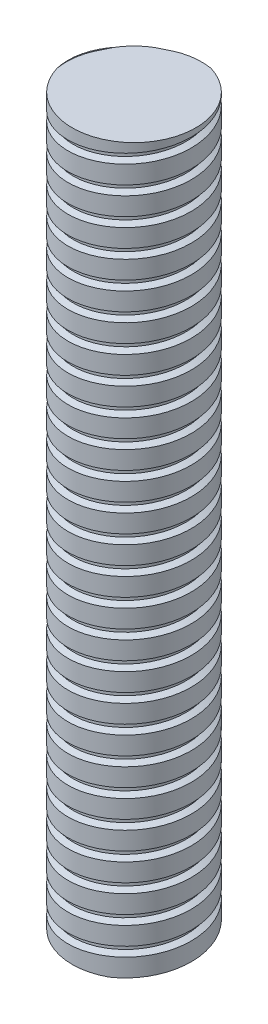
SolidWorks part; units mm, degrees
ref_plane "Plano frontal" through (0, 0, 0) normal (0, 0, 1) x (1, 0, 0)
ref_plane "Plano superior" through (0, 0, 0) normal (0, 1, 0) x (1, 0, 0)
ref_plane "Plano direito" through (0, 0, 0) normal (1, 0, 0) x (0, 0, -1)
sketch "Esboço1" plane through (0, 0, 0) normal (0, 1, 0) x (1, 0, 0)
  circle A0 centre (0, 0) radius 9
  dimension "D1" = 18
extrude "Ressalto-extrusão1" add sketch "Esboço1" along normal mid plane 105.5
sketch "Esboço2" plane through (0, -52.75, 0) normal (0, -1, 0) x (-1, 0, 0)
  circle A0 centre (0, 0) radius 9
  dimension "D1" = 18
curve "Hélice/Espiral1" pitch 4 height 105.5 turns 26.375
sketch "Esboço3" plane through (0, 0, 0) normal (1, 0, 0) x (0, 0, -1)
  line L0 (9, -51.065) -> (9, -52.435)
  line L1 (9, -52.435) -> (8.24, -52.005)
  line L2 (8.24, -52.005) -> (8.24, -51.495)
  line L3 (8.24, -51.495) -> (9, -51.065)
  point P3 (9, -51.75)
  dimension "D1" = 0.51
  dimension "D3" = 59
sweep "Varredura de corte1" cut profiles "Esboço3" path "Hélice/Espiral1"
sketch "Esboço4" plane through (0, -52.75, 0) normal (0, -1, 0) x (-1, 0, 0)
  circle A0 centre (0, 0) radius 2.55
  dimension "D1" = 5.1
extrude "Corte-extrusão1" cut sketch "Esboço4" against normal blind 20
